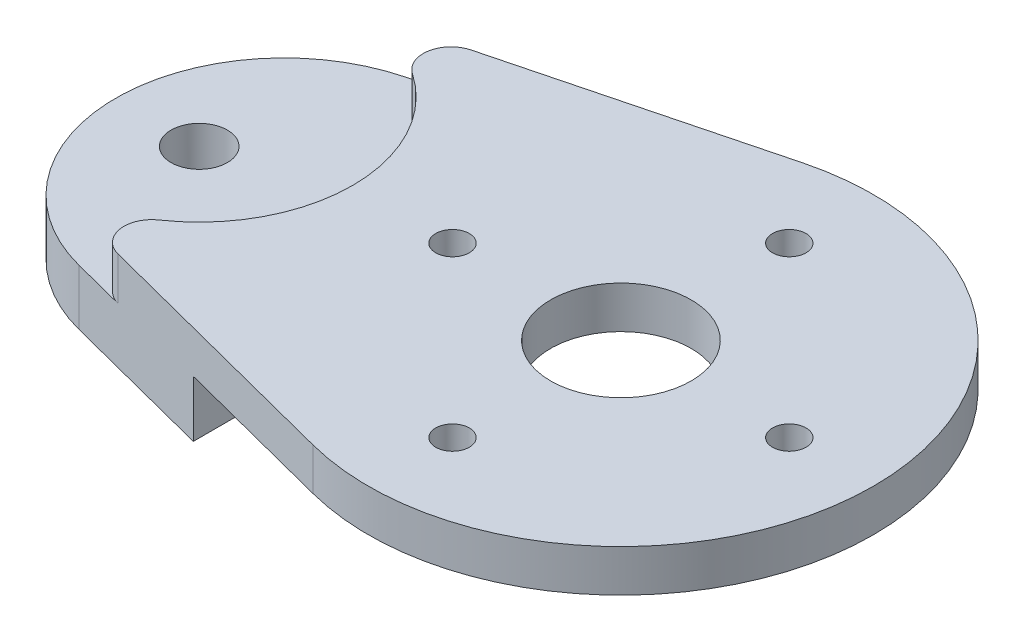
SolidWorks part; units mm, degrees
ref_plane "Front Plane" through (0, 0, 0) normal (0, 0, 1) x (1, 0, 0)
ref_plane "Top Plane" through (0, 0, 0) normal (0, 1, 0) x (1, 0, 0)
ref_plane "Right Plane" through (0, 0, 0) normal (1, 0, 0) x (0, 0, -1)
sketch "Sketch1" plane through (0, 0, 0) normal (0, 1, 0) x (1, 0, 0)
  line L0 (-14.986, 58.0405) -> (97.409, 87.0608)
  line L1 (-14.986, -58.0405) -> (97.409, -87.0608)
  arc A0 (-14.986, 58.0405) -> (-14.986, -58.0405) centre (0, 0) ccw
  arc A1 (97.409, -87.0608) -> (97.409, 87.0608) centre (119.888, 0) ccw
  dimension "D1" = 59.944
  dimension "D2" = 89.916
  dimension "D3" = 119.888
extrude "Boss-Extrude1" add sketch "Sketch1" along normal blind 35.052
sketch "Sketch2" plane through (0, 35.052, 0) normal (0, 1, 0) x (1, 0, 0)
  circle A0 centre (119.888, 0) radius 25.019
  circle A1 centre (-30.226, 0) radius 10.033
  arc A2 (97.409, -87.0608) -> (97.409, 87.0608) centre (119.888, 0) ccw construction
  dimension "D1" = 50.038
  dimension "D2" = 20.066
  dimension "D3" = 150.114
extrude "Cut-Extrude1" cut sketch "Sketch2" against normal through all and the other way through all
sketch "Sketch3" plane through (0, 35.052, 0) normal (0, 1, 0) x (1, 0, 0)
  arc A0 (-14.986, 58.0405) -> (-14.986, -58.0405) centre (0, 0) ccw construction
  arc A1 (-25.2207, 54.3801) -> (-25.2207, -54.3801) centre (0, 0) ccw
  arc A2 (-25.2207, 54.3801) -> (-25.2207, -54.3801) centre (-30.226, 0) cw
  dimension "D1" = 54.61
extrude "Cut-Extrude2" cut sketch "Sketch3" against normal blind 15.24
fillet "Fillet1" radius 9.906 2 edges at (-25.2207, 27.432, 54.3801) (-25.2207, 27.432, -54.3801)
sketch "Sketch5" plane through (0, 35.052, 0) normal (0, 1, 0) x (1, 0, 0)
  circle A0 centre (119.888, 0) radius 59.944 construction
  circle A1 centre (179.832, 0) radius 5.969
  dimension "D1" = 119.888
  dimension "D2" = 11.938
extrude "Cut-Extrude3" cut sketch "Sketch5" against normal through all
pattern_circular "CirPattern1" count 4 over 360 about axis through (119.888, 0, 0) along (0, 1, 0) of "Cut-Extrude3" reverse direction yes
sketch "Sketch6" plane through (0, 0, 0) normal (0, -1, 0) x (1, 0, 0)
  line L0 (119.888, 0) -> (0, 0) construction
  line L1 (39.878, -116.3275) -> (39.878, 116.3275)
  line L2 (39.878, 116.3275) -> (290.3539, 116.3275)
  line L3 (290.3539, 116.3275) -> (290.3539, -116.3275)
  line L4 (290.3539, -116.3275) -> (39.878, -116.3275)
  point P7 (39.878, 0)
extrude "Cut-Extrude4" cut sketch "Sketch6" against normal blind 20.066
